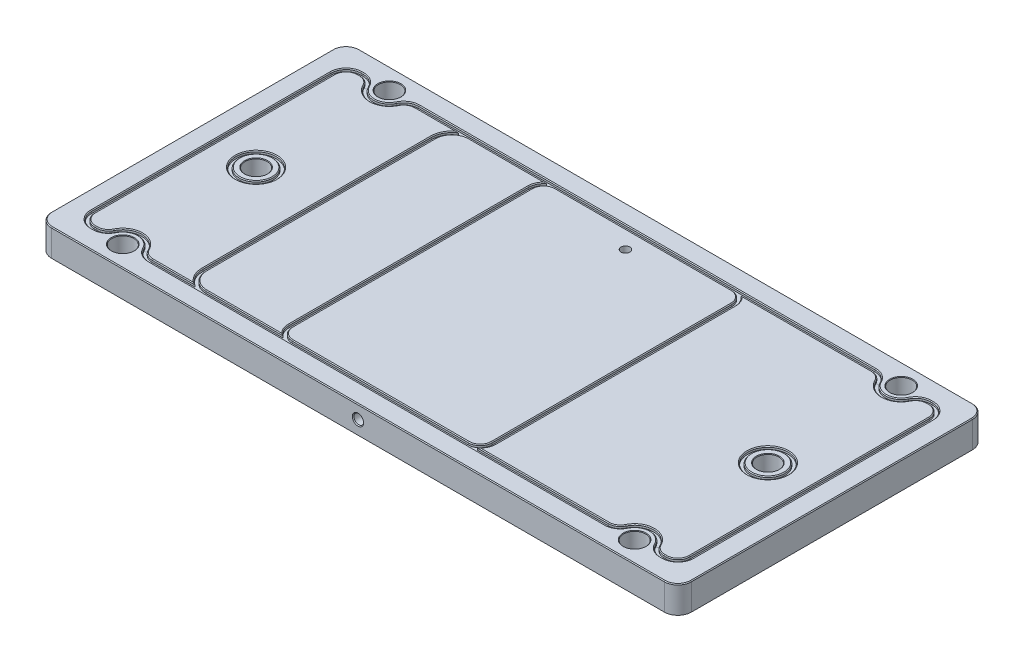
SolidWorks part; units mm, degrees
material "6061 Alloy"
ref_plane "Front Plane" through (0, 0, 0) normal (0, 0, 1) x (1, 0, 0)
ref_plane "Top Plane" through (0, 0, 0) normal (0, 1, 0) x (1, 0, 0)
ref_plane "Right Plane" through (0, 0, 0) normal (1, 0, 0) x (0, 0, -1)
sketch "Sketch1" plane through (0, 0, 0) normal (0, 1, 0) x (1, 0, 0)
  line L1 (-300.0375, -144.4625) -> (300.0375, -144.4625)
  line L2 (-300.0375, -144.4625) -> (-300.0375, 144.4625)
  line L3 (-300.0375, 144.4625) -> (300.0375, 144.4625)
  line L4 (300.0375, -144.4625) -> (300.0375, 144.4625)
  line L5 (-300.0375, -144.4625) -> (300.0375, 144.4625) construction
  line L6 (-300.0375, 144.4625) -> (300.0375, -144.4625) construction
  point P0 (0, 0)
  dimension "D1" = 288.925
  dimension "D2" = 600.075
extrude "Boss-Extrude1" add sketch "Sketch1" along normal blind 25.4
sketch "Sketch3" plane through (0, 25.4, 0) normal (0, 1, 0) x (1, 0, 0)
  line L0 (240, -125) -> (-240, -125) construction
  line L1 (-240, 0) -> (240, 0)
  line L2 (-240, 0) -> (-240, 125)
  line L3 (-240, 125) -> (240, 125)
  line L4 (240, 0) -> (240, 125)
  line L5 (-240, 0) -> (240, 125) construction
  line L6 (-240, 125) -> (240, 0) construction
  line L7 (-122.325, -144.4625) -> (-122.325, -125) construction
  line L8 (-300.0375, -144.4625) -> (300.0375, -144.4625) construction
  line L9 (120.1418, 144.4625) -> (120.1418, 125) construction
  line L10 (300.0375, 144.4625) -> (-300.0375, 144.4625) construction
  point P8 (-240, -125)
  point P9 (240, -125)
  dimension "D1" = 125
  dimension "D2" = 480
hole_wizard "CBORE for 1/2 Socket Head Cap Screw1" positions "Sketch4" profile "Sketch5" counterbore size "1/2" standard "ANSI Inch" end condition up to next
sketch "Sketch4" plane through (0, 25.4, 0) normal (0, 1, 0) x (1, 0, 0)
  point P0 (-240, 125)
  point P3 (-240, 0)
  point P6 (240, 125)
  point P9 (240, 0)
  point P12 (240, -125)
  point P15 (-240, -125)
sketch "Sketch5" plane through (-240, 25.4, -125) normal (1, 0, 0) x (0, 0, 1)
  line L0 (0, 0) -> (0, 25.4)
  line L1 (0, 25.4) -> (6.7462, 25.4)
  line L3 (6.7462, 25.4) -> (6.7462, 17.78)
  line L4 (6.7462, 17.78) -> (10.3187, 17.78)
  line L5 (10.3187, 17.78) -> (10.3187, 0)
  line L7 (10.3187, 0) -> (0, 0)
  line L11 (0, -6.35) -> (0, 107.95) construction
  dimension "Thru Hole Dia." = 13.4925
  dimension "Thru Hole Depth" = 25.4
  dimension "C'Bore Dia." = 20.6375
  dimension "C'Bore Depth" = 17.78
chamfer "Chamfer1" distance 0.508 angle 45 6 edges at (240, 25.4, 10.3188) (240, 25.4, -114.6812) (-240, 25.4, -114.6812) (-240, 25.4, 10.3188) (-240, 25.4, 135.3188) (240, 25.4, 135.3188)
sketch "Sketch6" plane through (0, 25.4, 0) normal (0, 1, 0) x (1, 0, 0)
  line L0 (0, 0) -> (64.3012, 0) construction
  line L1 (0, 0) -> (0, 66.2981) construction
fillet "Corner_Round_Over" radius 12.7 4 edges at (300.0375, 12.7, 144.4625) (-300.0375, 12.7, 144.4625) (300.0375, 12.7, -144.4625) (-300.0375, 12.7, -144.4625)
chamfer "Outside_Edge_Chamf" distance 0.762 angle 45 8 edges at (300.0375, 25.4, 0) (296.3178, 25.4, -140.7428) (296.3178, 25.4, 140.7428) (0, 25.4, -144.4625) (0, 25.4, 144.4625) (-296.3178, 25.4, -140.7428) (-296.3178, 25.4, 140.7428) (-300.0375, 25.4, 0)
sketch "Path" plane through (0, 25.4, 0) normal (0, 1, 0) x (1, 0, 0)
  line L0 (-90.2791, 143.7005) -> (-90.2791, 125) construction
  line L3 (0, 0) -> (41.9743, 0) construction
  line L4 (287.3375, 143.7005) -> (-287.3375, 143.7005) construction
  line L5 (-213.9761, 125) -> (213.9761, 125)
  line L9 (-213.9761, -125) -> (213.9761, -125)
  line L11 (0, 125) -> (0, 0) construction
  line L12 (0, 0) -> (0, -126.3568) construction
  line L13 (-299.2755, 82.7161) -> (-280.575, 82.7161) construction
  line L14 (-299.2755, 131.7625) -> (-299.2755, -131.7625) construction
  line L15 (-266.0239, 125) -> (-267.875, 125)
  line L16 (-280.575, 112.3) -> (-280.575, -112.3)
  line L17 (0, 0) -> (-280.575, 0) construction
  line L18 (-266.0239, -125) -> (-267.875, -125)
  line L19 (266.0239, 125) -> (267.875, 125)
  line L20 (280.575, 112.3) -> (280.575, -112.3)
  line L21 (266.0239, -125) -> (267.875, -125)
  arc A4 (-254.6105, 117.8699) -> (-225.3895, 117.8699) centre (-240, 125) ccw
  arc A5 (-266.0239, 125) -> (-254.6105, 117.8699) centre (-266.0239, 112.3) cw
  arc A6 (-267.875, 125) -> (-280.575, 112.3) centre (-267.875, 112.3) ccw
  arc A7 (-213.9761, 125) -> (-225.3895, 117.8699) centre (-213.9761, 112.3) ccw
  arc A8 (-213.9761, -125) -> (-225.3895, -117.8699) centre (-213.9761, -112.3) cw
  arc A9 (-254.6105, -117.8699) -> (-225.3895, -117.8699) centre (-240, -125) cw
  arc A10 (-266.0239, -125) -> (-254.6105, -117.8699) centre (-266.0239, -112.3) ccw
  arc A11 (-267.875, -125) -> (-280.575, -112.3) centre (-267.875, -112.3) cw
  arc A12 (213.9761, 125) -> (225.3895, 117.8699) centre (213.9761, 112.3) cw
  arc A13 (254.6105, 117.8699) -> (225.3895, 117.8699) centre (240, 125) cw
  arc A14 (266.0239, 125) -> (254.6105, 117.8699) centre (266.0239, 112.3) ccw
  arc A15 (267.875, 125) -> (280.575, 112.3) centre (267.875, 112.3) cw
  arc A16 (267.875, -125) -> (280.575, -112.3) centre (267.875, -112.3) ccw
  arc A17 (266.0239, -125) -> (254.6105, -117.8699) centre (266.0239, -112.3) cw
  arc A18 (254.6105, -117.8699) -> (225.3895, -117.8699) centre (240, -125) ccw
  arc A19 (213.9761, -125) -> (225.3895, -117.8699) centre (213.9761, -112.3) ccw
  point P28 (-256.2574, 125)
  point P33 (-223.7426, 125)
  point P61 (0, -125)
  dimension "D1" = 12.7
  dimension "D2" = 12.7
ref_plane "Plane1" through (0, 0, 0) normal (0, 0, 1) x (1, 0, 0)
sketch "Profile" plane through (0, 0, 0) normal (0, 0, 1) x (1, 0, 0)
  line L1 (-248.9447, 25.4) -> (-280.575, 25.4) construction
  line L2 (0, 25.4) -> (-280.575, 25.4) construction
  line L3 (-282.075, 22.86) -> (-279.075, 22.86)
  line L4 (-282.075, 22.86) -> (-282.075, 27.94)
  line L5 (-282.075, 27.94) -> (-279.075, 27.94)
  line L6 (-279.075, 22.86) -> (-279.075, 27.94)
  line L7 (-282.075, 22.86) -> (-279.075, 27.94) construction
  line L8 (-282.075, 27.94) -> (-279.075, 22.86) construction
  dimension "D1" = 5.08
  dimension "D2" = 3
sweep "Big Groove" cut profiles "Profile" path "Path"
chamfer "Big_Groove_Chamf" distance 0.762 angle 45 50 edges at (275.7946, 25.4, 120.2196) (279.075, 25.4, 0) (266.9494, 25.4, 123.5) (275.7946, 25.4, -120.2196) (260.0899, 25.4, 121.7988) (266.9494, 25.4, -123.5) (240, 25.4, 107.2426) (260.0899, 25.4, -121.7988) (219.9101, 25.4, 121.7988) (240, 25.4, -107.2426) (0, 25.4, 123.5) (219.9101, 25.4, -121.7988) (-219.9101, 25.4, 121.7988) (0, 25.4, -123.5) (-240, 25.4, 107.2426) (-219.9101, 25.4, -121.7988) (-260.0899, 25.4, 121.7988) (-240, 25.4, -107.2426) (-266.9494, 25.4, 123.5) (-260.0899, 25.4, -121.7988) (-275.7946, 25.4, 120.2196) (-266.9494, 25.4, -123.5) (-279.075, 25.4, 56.15) (-275.7946, 25.4, -120.2196) (-279.075, 25.4, -56.15) (282.075, 25.4, 0) (277.9159, 25.4, 122.3409) (277.9159, 25.4, -122.3409) (266.9494, 25.4, 126.5) (266.9494, 25.4, -126.5) (258.5004, 25.4, 124.3431) (258.5004, 25.4, -124.3431) (240, 25.4, 110.2426) (240, 25.4, -110.2426) (221.4996, 25.4, 124.3431) (221.4996, 25.4, -124.3431) (0, 25.4, 126.5) (0, 25.4, -126.5) (-221.4996, 25.4, 124.3431) (-221.4996, 25.4, -124.3431) (-240, 25.4, 110.2426) (-240, 25.4, -110.2426) (-258.5004, 25.4, 124.3431) (-258.5004, 25.4, -124.3431) (-266.9494, 25.4, 126.5) (-266.9494, 25.4, -126.5) (-277.9159, 25.4, 122.3409) (-277.9159, 25.4, -122.3409) (-282.075, 25.4, 56.15) (-282.075, 25.4, -56.15)
ref_plane "Plane2" through (0, 0, 0) normal (-1, 0, 0) x (0, 0, 1)
sketch "Sketch19" plane through (0, 25.4, 0) normal (0, 1, 0) x (1, 0, 0)
  circle A0 centre (-240, 0) radius 15.875
  circle A1 centre (-240, 0) radius 18.875
  dimension "D1" = 3
  dimension "D2" = 31.75
extrude "Small_Groove" cut sketch "Sketch19" against normal blind 2.54
chamfer "Sm_Groove_Chamf" distance 0.762 angle 45 2 edges at (-240, 25.4, 15.875) (-240, 25.4, 18.875)
sketch "Sketch11" plane through (0, 0, 144.4625) normal (0, 0, 1) x (1, 0, 0)
  line L0 (-287.3375, 25.4) -> (287.3375, 25.4) construction
  line L1 (-287.3375, 25.4) -> (287.3375, 25.4) construction
  line L2 (0, 25.4) -> (0, 0) construction
  line L3 (-287.3375, 0) -> (287.3375, 0) construction
  line L4 (0, 12.7) -> (7.1823, 12.7) construction
sketch "Sketch25" plane through (0, 0, -144.4625) normal (0, 0, -1) x (-1, 0, 0)
  line L0 (-287.3375, 25.4) -> (287.3375, 25.4) construction
  line L1 (-287.3375, 25.4) -> (287.3375, 25.4) construction
  line L2 (0, 25.4) -> (0, 0) construction
  line L3 (-287.3375, 0) -> (287.3375, 0) construction
  line L4 (0, 12.7) -> (18.0287, 12.7) construction
hole_wizard "1/8-27 NPSM Tapped Hole2" positions "Sketch26" profile "Sketch27" tap size "1/8-27 NPSM" standard "ANSI Inch"
sketch "Sketch26" plane through (0, 0, -144.4625) normal (0, 0, -1) x (-1, 0, 0)
  point P0 (0, 12.7)
sketch "Sketch27" plane through (0, 12.7, -144.4625) normal (1, 0, 0) x (0, 1, 0)
  line L0 (0, 0) -> (0, 53.5319)
  line L1 (0, 53.5319) -> (4.5466, 50.8)
  line L2 (4.5466, 50.8) -> (4.5466, 0)
  line L5 (4.5466, 0) -> (0, 0)
  line L10 (0, 53.5319) -> (-4.5466, 50.8) construction
  line L11 (0, -6.35) -> (0, 107.95) construction
  dimension "Tap Drill Dia." = 9.0932
  dimension "Tap Drill Depth" = 50.8
  dimension "Drill Angle" = 118
cosmetic thread "Hole Thread2" parameters "D1"=20.1676, "D2"=10.0838
sketch "Sketch28" plane through (0, 25.4, 0) normal (0, 1, 0) x (1, 0, 0)
  line L0 (-4.5466, 93.6625) -> (4.5466, 93.6625) construction
  line L1 (-4.5466, 93.6625) -> (4.5466, 93.6625) construction
  line L2 (0, 93.6625) -> (0, 106.3625) construction
  dimension "D1" = 12.7
hole_wizard "21/64 (0.32813) Diameter Hole1" positions "Sketch17" profile "Sketch18" hole size "21/64" standard "ANSI Inch"
sketch "Sketch17" plane through (0, 25.4, 0) normal (0, 1, 0) x (1, 0, 0)
  point P3 (0, 106.3625)
sketch "Sketch18" plane through (0, 25.4, -106.3625) normal (1, 0, 0) x (0, 0, 1)
  line L0 (0, 0) -> (0, 15.2039)
  line L1 (0, 15.2039) -> (4.1673, 12.7)
  line L2 (4.1673, 12.7) -> (4.1673, 0)
  line L5 (4.1673, 0) -> (0, 0)
  line L10 (0, 15.2039) -> (-4.1673, 12.7) construction
  line L11 (0, -6.35) -> (0, 107.95) construction
  dimension "Hole Dia." = 8.3345
  dimension "Hole Depth" = 12.7
  dimension "Drill Angle" = 118
mirror "Sm_Groove_Mirror" about plane through (0, 0, 0) normal (-1, 0, 0) of "Sm_Groove_Chamf", "Small_Groove"
sketch "Sketch20" plane through (0, 0, 144.4625) normal (0, 0, 1) x (1, 0, 0)
  line L0 (-287.3375, 0) -> (287.3375, 0) construction
  line L1 (-287.3375, 0) -> (300.0375, 0)
  line L2 (300.0375, 24.638) -> (300.0375, 0) construction
  line L3 (300.0375, 24.638) -> (300.0375, 0)
sketch "Path-2" plane through (0, 25.4, 0) normal (0, 1, 0) x (1, 0, 0)
  line L0 (-141.2875, 127.262) -> (-141.2875, 122.738) construction
  line L1 (-213.9761, 127.262) -> (213.9761, 127.262) construction
  line L2 (213.9761, 122.738) -> (-213.9761, 122.738) construction
  line L3 (-141.2875, -122.738) -> (-141.2875, -127.262) construction
  line L4 (-213.9761, -122.738) -> (213.9761, -122.738) construction
  line L5 (213.9761, -127.262) -> (-213.9761, -127.262) construction
  line L6 (-141.2875, 125) -> (-163.5125, 125)
  line L7 (-181.2925, 107.22) -> (-181.2925, -107.22)
  line L8 (-141.2875, -125) -> (-163.5125, -125)
  line L9 (-300.0375, -131.7625) -> (-300.0375, 131.7625) construction
  arc A0 (-163.5125, -125) -> (-181.2925, -107.22) centre (-163.5125, -107.22) cw
  arc A1 (-163.5125, 125) -> (-181.2925, 107.22) centre (-163.5125, 107.22) ccw
  dimension "D1" = 17.78
  dimension "D2" = 118.745
  dimension "D3" = 158.75
ref_plane "Plane3" through (-141.2875, 0, 0) normal (-1, 0, 0) x (0, 0, 1)
sketch "Profile_2" plane through (-141.2875, 0, 0) normal (-1, 0, 0) x (0, 0, 1)
  line L1 (-123.5, 27.94) -> (-126.5, 27.94)
  line L2 (-123.5, 27.94) -> (-123.5, 22.86)
  line L3 (-123.5, 22.86) -> (-126.5, 22.86)
  line L4 (-126.5, 27.94) -> (-126.5, 22.86)
  line L5 (-123.5, 27.94) -> (-126.5, 22.86) construction
  line L6 (-123.5, 22.86) -> (-126.5, 27.94) construction
  point P0 (-125, 25.4)
  dimension "D1" = 5.08
  dimension "D2" = 3
sweep "Sub_Groove" cut profiles "Profile_2" path "Path-2"
chamfer "Chamfer6" distance 0.762 angle 45 6 edges at (-176.6498, 25.4, -116.8351) (-179.7925, 25.4, 0) (-176.6498, 25.4, 116.8351) (-180.7217, 25.4, -115.9127) (-182.7925, 25.4, 0) (-180.7217, 25.4, 115.9127)
sketch "Sketch23" plane through (0, 25.4, 0) normal (0, 1, 0) x (1, 0, 0)
  line L0 (0, 0) -> (0, -41.1056) construction
  line L1 (0, 0) -> (75.2313, 0) construction
ref_plane "Plane4" through (-71.4375, 0, 0) normal (-1, 0, 0) x (0, 0, 1)
mirror "Sub_Groove_Mirror" [suppressed] about plane through (-71.4375, 0, 0) normal (-1, 0, 0)
sketch "Sketch24" plane through (0, 25.4, 0) normal (0, 1, 0) x (1, 0, 0)
  line L0 (-299.2755, 0) -> (299.2755, 0) construction
  line L1 (-299.2755, 131.7625) -> (-299.2755, -131.7625) construction
  line L2 (299.2755, -131.7625) -> (299.2755, 131.7625) construction
  line L3 (0, 0) -> (0, 50.0766) construction
sketch "Groove_Path" plane through (0, 25.4, 0) normal (0, 1, 0) x (1, 0, 0)
  line L0 (299.2755, 0) -> (-299.2755, 0) construction
  line L1 (299.2755, -131.7625) -> (299.2755, 131.7625) construction
  line L2 (-299.2755, 131.7625) -> (-299.2755, -131.7625) construction
  line L3 (0, 0) -> (0, -20.7323) construction
  line L5 (82.55, 125) -> (-82.55, 125)
  line L6 (95.25, 112.3) -> (95.25, -112.3)
  line L7 (82.55, -125) -> (-82.55, -125)
  line L8 (-95.25, 112.3) -> (-95.25, -112.3)
  line L9 (95.25, 125) -> (-95.25, -125) construction
  line L10 (95.25, -125) -> (-95.25, 125) construction
  arc A0 (95.25, -112.3) -> (82.55, -125) centre (82.55, -112.3) cw
  arc A1 (82.55, 125) -> (95.25, 112.3) centre (82.55, 112.3) cw
  arc A2 (-82.55, 125) -> (-95.25, 112.3) centre (-82.55, 112.3) ccw
  arc A3 (-82.55, -125) -> (-95.25, -112.3) centre (-82.55, -112.3) cw
  dimension "D3" = 12.7
  dimension "D1" = 250
  dimension "D2" = 190.5
sketch "Groove_Profile" plane through (-71.4375, 0, 0) normal (-1, 0, 0) x (0, 0, 1)
  line L0 (-126.5, 22.86) -> (-123.5, 22.86) construction
  line L1 (-126.5, 22.86) -> (-123.5, 22.86)
  line L2 (-126.5, 22.86) -> (-126.5, 27.94)
  line L3 (-123.5, 22.86) -> (-123.5, 27.94)
  line L4 (-123.5, 27.94) -> (-126.5, 27.94)
  dimension "D1" = 5.08
sweep "Cut-Sweep1" cut profiles "Groove_Profile" path "Groove_Path"
chamfer "Chamfer7" distance 0.762 angle 45 12 edges at (95.5567, 25.4, 117.9978) (95.5567, 25.4, -117.9978) (96.75, 25.4, 0) (-95.5567, 25.4, -117.9978) (-95.5567, 25.4, 117.9978) (-96.75, 25.4, 0) (-91.7944, 25.4, 118.623) (-91.7944, 25.4, -118.623) (-93.75, 25.4, 0) (91.7944, 25.4, -118.623) (91.7944, 25.4, 118.623) (93.75, 25.4, 0)
sketch "TSlots_NoGo_Area" plane through (0, 0, 0) normal (0, -1, 0) x (1, 0, 0)
  line L0 (240, 0) -> (-240, 0) construction
  line L1 (240, -125) -> (-240, -125) construction
  line L2 (240, 125) -> (-240, 125) construction
  line L4 (457.2, 12.7) -> (-457.2, 12.7)
  line L5 (457.2, 12.7) -> (457.2, -12.7)
  line L6 (457.2, -12.7) -> (-457.2, -12.7)
  line L7 (-457.2, 12.7) -> (-457.2, -12.7)
  line L8 (457.2, 12.7) -> (-457.2, -12.7) construction
  line L9 (457.2, -12.7) -> (-457.2, 12.7) construction
  line L10 (457.2, -137.7) -> (-457.2, -137.7)
  line L11 (457.2, -137.7) -> (457.2, -112.3)
  line L12 (457.2, -112.3) -> (-457.2, -112.3)
  line L13 (-457.2, -137.7) -> (-457.2, -112.3)
  line L14 (457.2, -137.7) -> (-457.2, -112.3) construction
  line L15 (457.2, -112.3) -> (-457.2, -137.7) construction
  line L16 (457.2, 137.7) -> (-457.2, 137.7)
  line L17 (457.2, 137.7) -> (457.2, 112.3)
  line L18 (457.2, 112.3) -> (-457.2, 112.3)
  line L19 (-457.2, 137.7) -> (-457.2, 112.3)
  line L20 (457.2, 137.7) -> (-457.2, 112.3) construction
  line L21 (457.2, 112.3) -> (-457.2, 137.7) construction
  point P12 (0, 0)
  point P17 (0, -125)
  point P23 (0, 125)
  dimension "D1" = 25.4
  dimension "D2" = 25.4
  dimension "D3" = 914.4
  dimension "D4" = 25.4
  dimension "D5" = 914.4
sketch "Bottom_Slot_Path" plane through (0, 0, 0) normal (0, -1, 0) x (1, 0, 0)
  line L0 (0, 0) -> (0, -125) construction
  line L2 (-260.35, -100.6) -> (260.35, -100.6)
  line L3 (-273.05, -87.9) -> (-273.05, -37.1)
  line L4 (-260.35, -24.4) -> (260.35, -24.4)
  line L5 (273.05, -87.9) -> (273.05, -37.1)
  line L6 (-273.05, -100.6) -> (273.05, -24.4) construction
  line L7 (-273.05, -24.4) -> (273.05, -100.6) construction
  arc A0 (260.35, -100.6) -> (273.05, -87.9) centre (260.35, -87.9) ccw
  arc A1 (260.35, -24.4) -> (273.05, -37.1) centre (260.35, -37.1) cw
  arc A2 (-260.35, -100.6) -> (-273.05, -87.9) centre (-260.35, -87.9) cw
  arc A3 (-273.05, -37.1) -> (-260.35, -24.4) centre (-260.35, -37.1) cw
  point P4 (0, -62.5)
  dimension "D1" = 12.7
  dimension "D2" = 546.1
  dimension "D3" = 76.2
sketch "Bottom_Slot_Profile" plane through (-141.2875, 0, 0) normal (-1, 0, 0) x (0, 0, 1)
  line L5 (-99.1, -2.54) -> (-102.1, -2.54)
  line L6 (-99.1, -2.54) -> (-99.1, 2.54)
  line L7 (-99.1, 2.54) -> (-102.1, 2.54)
  line L8 (-102.1, -2.54) -> (-102.1, 2.54)
  line L9 (-99.1, -2.54) -> (-102.1, 2.54) construction
  line L10 (-99.1, 2.54) -> (-102.1, -2.54) construction
  point P0 (-100.6, 0)
  point P2 (-100.6, 0)
  dimension "D1" = 5.08
  dimension "D2" = 3
sweep "Bottom_Groove_Front" cut profiles "Bottom_Slot_Profile" path "Bottom_Slot_Path"
chamfer "Chamfer8" distance 0.762 angle 45 18 edges at (59.5312, 0, -99.1) (-200.8188, 0, -99.1) (268.2696, 0, -95.8196) (-268.2696, 0, -95.8196) (271.55, 0, -62.5) (-271.55, 0, -62.5) (268.2696, 0, -29.1804) (-268.2696, 0, -29.1804) (0, 0, -25.9) (-200.8188, 0, -102.1) (59.5312, 0, -102.1) (-270.3909, 0, -97.9409) (270.3909, 0, -97.9409) (-274.55, 0, -62.5) (274.55, 0, -62.5) (-270.3909, 0, -27.0591) (270.3909, 0, -27.0591) (0, 0, -22.9)
sketch "Sketch34" plane through (0, 0, 0) normal (0, -1, 0) x (1, 0, 0)
  line L0 (0, -144.4625) -> (0, -93.6625) construction
  line L1 (287.3375, -144.4625) -> (-287.3375, -144.4625) construction
  line L2 (0, -93.6625) -> (0, -90.4875) construction
  dimension "D1" = 50.8
  dimension "D2" = 3.175
hole_wizard "1/4-20 Tapped Hole1" positions "Sketch35" profile "Sketch36" tap size "1/4-20" standard "ANSI Inch"
sketch "Sketch35" plane through (0, 0, 0) normal (0, -1, 0) x (-1, 0, 0)
  point P0 (0, 90.4875)
sketch "Sketch36" plane through (0, 0, -90.4875) normal (1, 0, 0) x (0, 0, -1)
  line L0 (0, 0) -> (0, 14.2338)
  line L1 (0, 14.2338) -> (2.5527, 12.7)
  line L2 (2.5527, 12.7) -> (2.5527, 0)
  line L5 (2.5527, 0) -> (0, 0)
  line L10 (0, 14.2338) -> (-2.5527, 12.7) construction
  line L11 (0, -6.35) -> (0, 107.95) construction
  dimension "Tap Drill Dia." = 5.1054
  dimension "Tap Drill Depth" = 12.7
  dimension "Drill Angle" = 118
chamfer "Chamfer9" distance 0.762 angle 45 1 edges at (0, 0, -93.0402)
sketch "Bottom_Slot_Path2" plane through (0, 0, 0) normal (0, -1, 0) x (1, 0, 0)
  line L0 (457.2, 112.3) -> (-457.2, 112.3) construction
  line L1 (457.2, 112.3) -> (-457.2, 112.3) construction
  line L2 (457.2, 12.7) -> (-457.2, 12.7) construction
  line L3 (457.2, 12.7) -> (-457.2, 12.7) construction
  line L4 (0, 112.3) -> (0, 12.7) construction
  line L6 (-260.35, 24.4) -> (260.35, 24.4)
  line L7 (-273.05, 37.1) -> (-273.05, 87.9)
  line L8 (-260.35, 100.6) -> (260.35, 100.6)
  line L9 (273.05, 37.1) -> (273.05, 87.9)
  line L10 (-273.05, 24.4) -> (273.05, 100.6) construction
  line L11 (-273.05, 100.6) -> (273.05, 24.4) construction
  arc A0 (260.35, 24.4) -> (273.05, 37.1) centre (260.35, 37.1) ccw
  arc A1 (260.35, 100.6) -> (273.05, 87.9) centre (260.35, 87.9) cw
  arc A2 (-260.35, 24.4) -> (-273.05, 37.1) centre (-260.35, 37.1) cw
  arc A3 (-273.05, 87.9) -> (-260.35, 100.6) centre (-260.35, 87.9) cw
  point P6 (0, 62.5)
  dimension "D3" = 12.7
  dimension "D1" = 76.2
  dimension "D2" = 546.1
sketch "Bottom_Slot_Profile2" plane through (-71.4375, 0, 0) normal (-1, 0, 0) x (0, 0, 1)
  line L1 (25.9, -2.54) -> (22.9, -2.54)
  line L2 (25.9, -2.54) -> (25.9, 2.54)
  line L3 (25.9, 2.54) -> (22.9, 2.54)
  line L4 (22.9, -2.54) -> (22.9, 2.54)
  line L5 (25.9, -2.54) -> (22.9, 2.54) construction
  line L6 (25.9, 2.54) -> (22.9, -2.54) construction
  point P0 (24.4, 0)
  point P2 (24.4, 0)
  dimension "D1" = 5.08
  dimension "D2" = 3
sweep "Cut-Sweep3" cut profiles "Bottom_Slot_Profile2" path "Bottom_Slot_Path2"
chamfer "Chamfer10" distance 0.762 angle 45 18 edges at (271.55, 0, 62.5) (268.2696, 0, 29.1804) (268.2696, 0, 95.8196) (94.4562, 0, 25.9) (0, 0, 99.1) (-165.8938, 0, 25.9) (-268.2696, 0, 95.8196) (-268.2696, 0, 29.1804) (-271.55, 0, 62.5) (-165.8937, 0, 22.9) (94.4562, 0, 22.9) (-270.3909, 0, 27.0591) (270.3909, 0, 27.0591) (-274.55, 0, 62.5) (274.55, 0, 62.5) (-270.3909, 0, 97.9409) (270.3909, 0, 97.9409) (0, 0, 102.1)
hole_wizard "1/8-27 NPSM Tapped Hole3" positions "Sketch41" profile "Sketch42" tap size "1/8-27 NPSM" standard "ANSI Inch"
sketch "Sketch41" plane through (0, 0, 144.4625) normal (0, 0, 1) x (1, 0, 0)
  point P0 (0, 12.7)
sketch "Sketch42" plane through (0, 12.7, 144.4625) normal (1, 0, 0) x (0, -1, 0)
  line L0 (0, 0) -> (0, 53.5319)
  line L1 (0, 53.5319) -> (4.5466, 50.8)
  line L2 (4.5466, 50.8) -> (4.5466, 0)
  line L5 (4.5466, 0) -> (0, 0)
  line L10 (0, 53.5319) -> (-4.5466, 50.8) construction
  line L11 (0, -6.35) -> (0, 107.95) construction
  dimension "Tap Drill Dia." = 9.0932
  dimension "Tap Drill Depth" = 50.8
  dimension "Drill Angle" = 118
cosmetic thread "Hole Thread3" parameters "D1"=20.1676, "D2"=10.0838
sketch "Sketch43" plane through (0, 0, 0) normal (0, -1, 0) x (1, 0, 0)
  line L0 (4.5466, 93.6625) -> (-4.5466, 93.6625) construction
  line L1 (4.5466, 93.6625) -> (-4.5466, 93.6625) construction
  line L2 (0, 93.6625) -> (0, 90.4875) construction
  dimension "D1" = 3.175
hole_wizard "1/4-20 Tapped Hole2" positions "Sketch44" profile "Sketch45" tap size "1/4-20" standard "ANSI Inch"
sketch "Sketch44" plane through (0, 0, 0) normal (0, -1, 0) x (-1, 0, 0)
  point P0 (0, -90.4875)
sketch "Sketch45" plane through (0, 0, 90.4875) normal (1, 0, 0) x (0, 0, -1)
  line L0 (0, 0) -> (0, 14.2338)
  line L1 (0, 14.2338) -> (2.5527, 12.7)
  line L2 (2.5527, 12.7) -> (2.5527, 0)
  line L5 (2.5527, 0) -> (0, 0)
  line L10 (0, 14.2338) -> (-2.5527, 12.7) construction
  line L11 (0, -6.35) -> (0, 107.95) construction
  dimension "Tap Drill Dia." = 5.1054
  dimension "Tap Drill Depth" = 12.7
  dimension "Drill Angle" = 118
cosmetic thread "Hole Thread4" parameters "D1"=12.7, "D2"=6.35
chamfer "Chamfer11" distance 0.762 angle 45 3 edges at (0, 0, 87.9348) (-4.5466, 12.7, -144.4625) (4.5466, 12.7, 144.4625)
sketch "Sketch46" plane through (0, 0, 0) normal (0, -1, 0) x (1, 0, 0)
  line L0 (0, 144.4625) -> (0, -144.4625) construction
  line L1 (-287.3375, 144.4625) -> (287.3375, 144.4625) construction
  line L2 (287.3375, -144.4625) -> (-287.3375, -144.4625) construction
  line L3 (0, 0) -> (59.313, 0) construction
fillet "Fillet2" radius 1.1906 18 edges at (268.2696, 2.54, 95.8196) (271.55, 2.54, 62.5) (268.2696, 2.54, 29.1804) (94.4562, 2.54, 25.9) (-165.8937, 2.54, 25.9) (-268.2696, 2.54, 29.1804) (-271.55, 2.54, 62.5) (-268.2696, 2.54, 95.8196) (270.3909, 2.54, 97.9409) (274.55, 2.54, 62.5) (270.3909, 2.54, 27.0591) (94.4562, 2.54, 22.9) (-165.8937, 2.54, 22.9) (-270.3909, 2.54, 27.0591) (-274.55, 2.54, 62.5) (-270.3909, 2.54, 97.9409) (0, 2.54, 99.1) (0, 2.54, 102.1)
